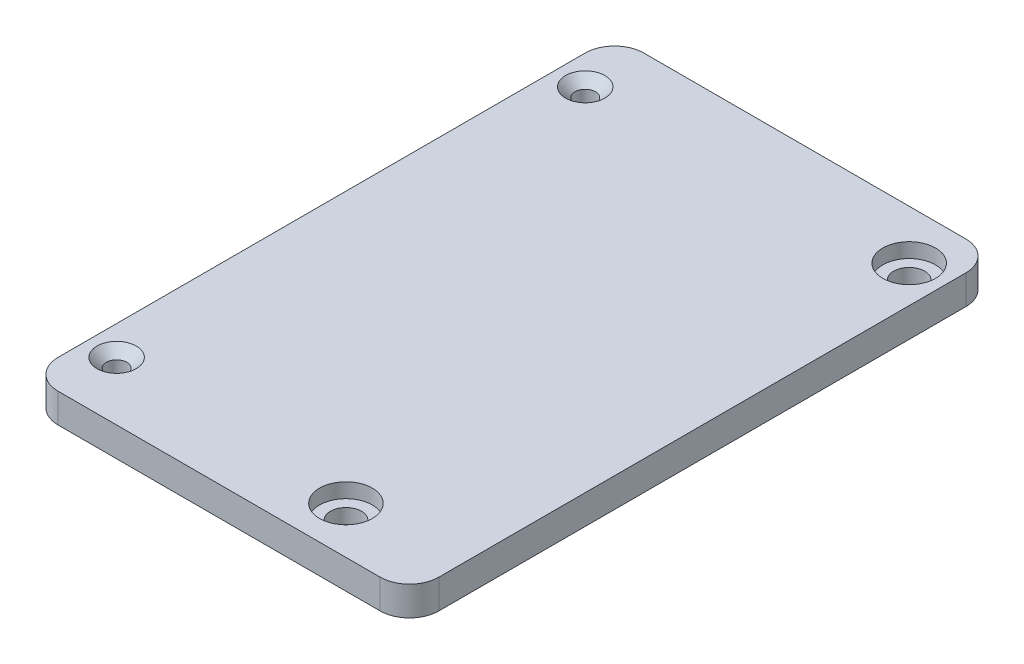
SolidWorks part; units mm, degrees
ref_plane "Front Plane" through (0, 0, 0) normal (0, 0, 1) x (1, 0, 0)
ref_plane "Top Plane" through (0, 0, 0) normal (0, 1, 0) x (1, 0, 0)
ref_plane "Right Plane" through (0, 0, 0) normal (1, 0, 0) x (0, 0, -1)
sketch "Sketch2" plane through (0, 0, 0) normal (0, 1, 0) x (1, 0, 0)
  line L1 (-32.5, 50) -> (32.5, 50)
  line L2 (-32.5, 50) -> (-32.5, -50)
  line L3 (-32.5, -50) -> (32.5, -50)
  line L4 (32.5, 50) -> (32.5, -50)
  line L5 (-32.5, 50) -> (32.5, -50) construction
  line L6 (-32.5, -50) -> (32.5, 50) construction
  circle A0 centre (-27.5, 40) radius 1.75
  circle A1 centre (-27.5, -40) radius 1.75
  circle A2 centre (26.23, 41.58) radius 2.65
  circle A3 centre (13.65, -42) radius 2.65
  point P0 (0, 0)
  dimension "D3" = 3.5
  dimension "D4" = 5
  dimension "D8" = 5.3
  dimension "D9" = 5.3
  dimension "D1" = 65
  dimension "D2" = 100
  dimension "D5" = 5
  dimension "D6" = 10
  dimension "D7" = 10
  dimension "D10" = 46.15
  dimension "D11" = 8
  dimension "D12" = 8.42
  dimension "D13" = 6.27
extrude "Boss-Extrude1" add sketch "Sketch2" along normal blind 5
sketch "Sketch3" plane through (0, 5, 0) normal (0, 1, 0) x (1, 0, 0)
  circle A0 centre (26.23, 41.58) radius 4.5
  circle A1 centre (13.65, -42) radius 4.5
  dimension "D1" = 9
  dimension "D2" = 9
extrude "Cut-Extrude1" cut sketch "Sketch3" against normal blind 2.5
fillet "Fillet1" radius 5 4 edges at (-32.5, 2.5, 50) (-32.5, 2.5, -50) (32.5, 2.5, -50) (32.5, 2.5, 50)
chamfer "Chamfer1" distance 1.6 angle 45 2 edges at (-27.5, 5, 41.75) (-27.5, 5, -38.25)
